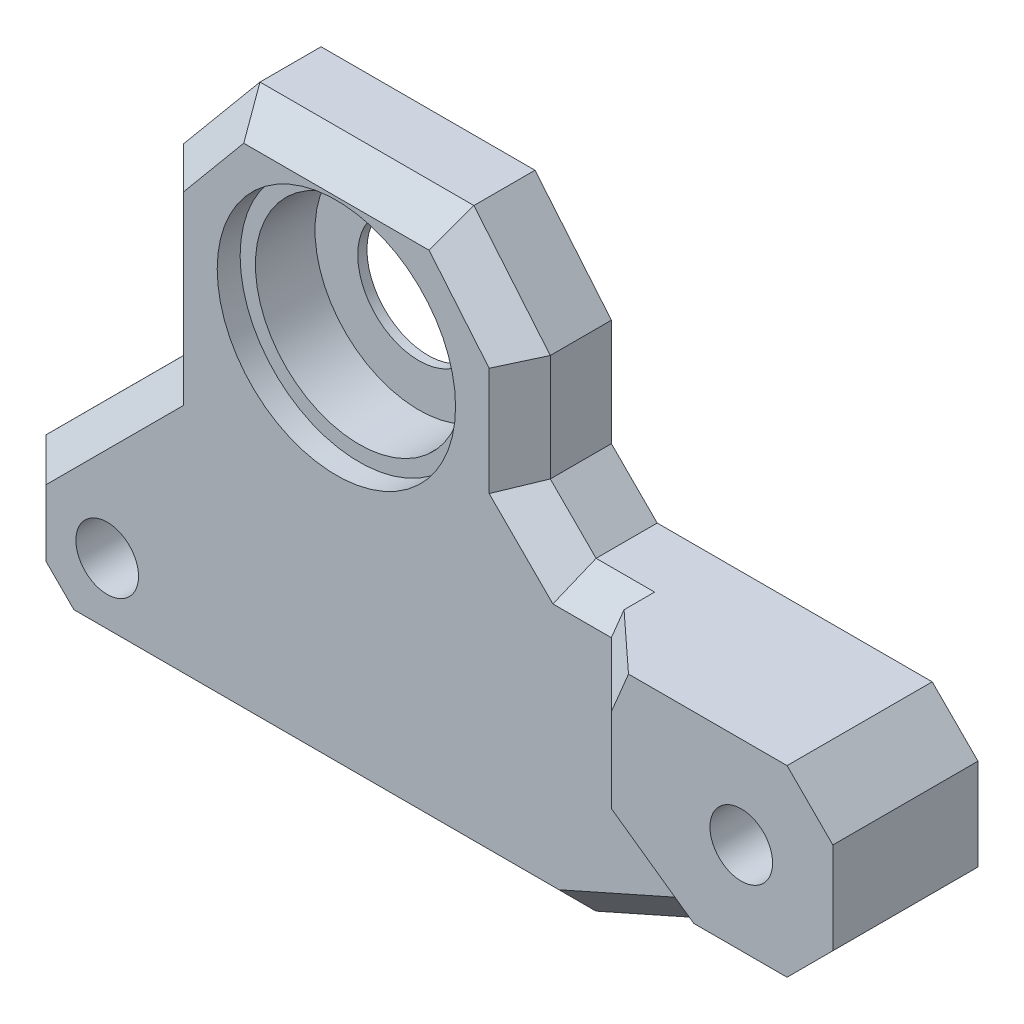
SolidWorks part; units mm, degrees
material "AISI 1020"
ref_plane "Front Plane" through (0, 0, 0) normal (0, 0, 1) x (1, 0, 0)
ref_plane "Top Plane" through (0, 0, 0) normal (0, 1, 0) x (1, 0, 0)
ref_plane "Right Plane" through (0, 0, 0) normal (1, 0, 0) x (0, 0, -1)
sketch "Sketch1" plane through (0, 0, 0) normal (0, 0, 1) x (1, 0, 0)
  line L0 (0, 14.0272) -> (0, -12.6873) construction
  line L1 (7, 15.5362) -> (-7, 15.5362)
  line L2 (-7, 15.5362) -> (-12, 9.5365)
  line L3 (-12, 0) -> (12, 0) construction
  line L4 (-12, 9.5365) -> (-12, -2.4635)
  line L6 (-21.0056, -11.4638) -> (-21.0056, -17.4638)
  line L7 (-21.0056, -17.4638) -> (-18.0093, -20.4638)
  line L8 (35.9944, -9.4616) -> (32.9963, -12.4598)
  line L9 (7, 15.5362) -> (12, 9.5365)
  line L10 (12, 9.5365) -> (12, 2.5365)
  line L11 (12, 2.5365) -> (14.9981, -0.4616)
  line L12 (14.9981, -0.4616) -> (32.9981, -0.4616)
  line L13 (32.9981, -0.4616) -> (35.9944, -3.4616)
  line L14 (35.9944, -3.4616) -> (35.9944, -9.4616)
  line L15 (32.9963, -12.4598) -> (14.9907, -20.4638)
  line L16 (14.9907, -20.4638) -> (-18.0093, -20.4638)
  line L17 (-12, -2.4635) -> (-21.0056, -11.4638)
  point P8 (0, 15.5362)
  point P13 (-12, -2.4635)
  dimension "D1" = 14
  dimension "D2" = 24
  dimension "D3" = 36
  dimension "D4" = 12
  dimension "D5" = 7.81
  dimension "D6" = 6
  dimension "D7" = 57
  dimension "D8" = 33
  dimension "D9" = 4.24
  dimension "D10" = 3
  dimension "D11" = 7
  dimension "D12" = 4.24
  dimension "D13" = 2.9981
  dimension "D14" = 18
  dimension "D15" = 4.24
  dimension "D16" = 3
  dimension "D17" = 6
  dimension "D18" = 4.24
  dimension "D19" = 2.9981
extrude "Boss-Extrude1" add sketch "Sketch1" against normal blind 4
sketch "Sketch2" plane through (0, 0, 0) normal (0, 0, 1) x (1, 0, 0)
  line L0 (7, 15.5362) -> (12, 9.5365) construction
  line L1 (12, 9.5365) -> (12, 2.5365) construction
  line L2 (12, 2.5365) -> (14.9981, -0.4616) construction
  line L3 (14.9981, -0.4616) -> (32.9981, -0.4616) construction
  line L4 (32.9981, -0.4616) -> (35.9944, -3.4616) construction
  line L5 (35.9944, -3.4616) -> (35.9944, -9.4616) construction
  line L6 (35.9944, -9.4616) -> (32.9963, -12.4598) construction
  line L7 (32.9963, -12.4598) -> (14.9907, -20.4638) construction
  line L8 (14.9907, -20.4638) -> (-18.0093, -20.4638) construction
  line L9 (-21.0056, -17.4638) -> (-18.0093, -20.4638) construction
  line L10 (-21.0056, -11.4638) -> (-21.0056, -17.4638) construction
  line L11 (-12, -2.4635) -> (-21.0056, -11.4638) construction
  line L12 (-12, 9.5365) -> (-12, -2.4635) construction
  line L13 (-7, 15.5362) -> (-12, 9.5365) construction
  line L14 (7, 15.5362) -> (-7, 15.5362) construction
  line L15 (7, 15.5362) -> (12, 9.5365)
  line L16 (12, 9.5365) -> (12, 2.5365)
  line L17 (12, 2.5365) -> (14.9981, -0.4616)
  line L18 (14.9981, -0.4616) -> (32.9981, -0.4616)
  line L19 (32.9981, -0.4616) -> (35.9944, -3.4616)
  line L20 (35.9944, -3.4616) -> (35.9944, -9.4616)
  line L21 (35.9944, -9.4616) -> (32.9963, -12.4598)
  line L22 (32.9963, -12.4598) -> (14.9907, -20.4638)
  line L23 (14.9907, -20.4638) -> (-18.0093, -20.4638)
  line L24 (-21.0056, -17.4638) -> (-18.0093, -20.4638)
  line L25 (-21.0056, -11.4638) -> (-21.0056, -17.4638)
  line L26 (-12, -2.4635) -> (-21.0056, -11.4638)
  line L27 (-12, 9.5365) -> (-12, -2.4635)
  line L28 (-7, 15.5362) -> (-12, 9.5365)
  line L29 (7, 15.5362) -> (-7, 15.5362)
extrude "Boss-Extrude2" add sketch "Sketch2" along normal blind 2 draft 45
sketch "Sketch4" plane through (0, 0, 0) normal (0, 0, 1) x (1, 0, 0)
  line L1 (14.9981, -0.4616) -> (32.9981, -0.4616) construction
  line L4 (32.9963, -12.4598) -> (20.8263, -12.4598)
  line L6 (18.8281, -0.4616) -> (32.9981, -0.4616)
  line L7 (32.9981, -0.4616) -> (35.9944, -3.4616)
  line L8 (35.9944, -3.4616) -> (35.9944, -9.4616)
  line L9 (35.9944, -9.4616) -> (32.9963, -12.4598)
  line L10 (18.8281, -0.4616) -> (17.9963, -2.4598)
  line L11 (17.9963, -2.4598) -> (17.9963, -10.4598)
  line L12 (17.9963, -10.4598) -> (20.8263, -12.4598)
  dimension "D1" = 14.17
  dimension "D2" = 12.17
  dimension "D3" = 8
  dimension "D4" = 2.83
  dimension "D5" = 2
extrude "Boss-Extrude3" add sketch "Sketch4" along normal blind 5.5
sketch "Sketch6" plane through (0, 0, -4) normal (0, 0, -1) x (-1, 0, 0)
  line L0 (0, 14.0272) -> (0, -12.6873) construction
  circle A0 centre (0, 5.54) radius 4
  point P1 (0, 15.5362)
  dimension "D2" = 5.54
  dimension "D1" = 15.5362
extrude "Cut-Extrude1" cut sketch "Sketch6" against normal blind 18.5
sketch "Sketch7" plane through (0, 0, 2) normal (0, 0, 1) x (1, 0, 0)
  circle A0 centre (0, 5.54) radius 6.8
extrude "Cut-Extrude2" cut sketch "Sketch7" against normal blind 5.4
sketch "Sketch8" plane through (0, 0, 2) normal (0, 0, 1) x (1, 0, 0)
  circle A0 centre (0, 5.54) radius 7.8
extrude "Cut-Extrude3" cut sketch "Sketch8" against normal blind 1.5
sketch "Sketch9" plane through (0, 0, 5.5) normal (0, 0, 1) x (1, 0, 0)
  line L0 (0, 14.0272) -> (0, -12.6873) construction
  circle A0 centre (-15, -14.46) radius 2.05
  circle A1 centre (30, -6.46) radius 2.05
  point P4 (0, 0)
  point P5 (0, 0)
  point P6 (0, 0)
  dimension "D1" = 45
  dimension "D2" = 12
  dimension "D3" = 20
  dimension "D4" = 15
extrude "Cut-Extrude4" cut sketch "Sketch9" against normal blind 15.5
sketch "Sketch10" plane through (0, 0, -4) normal (0, 0, -1) x (-1, 0, 0)
  circle A0 centre (15, -14.46) radius 4
extrude "Cut-Extrude5" cut sketch "Sketch10" against normal blind 2
sketch "Sketch11" plane through (0, 0, -4) normal (0, 0, -1) x (-1, 0, 0)
  circle A0 centre (-30, -6.46) radius 4
extrude "Cut-Extrude6" cut sketch "Sketch11" against normal blind 2
chamfer "Chamfer4" distance 3.5 angle 45 3 edges at (19.4113, -11.4598, 5.5) (18.4122, -1.4607, 5.5) (17.9963, -6.4598, 5.5)
equation "\"A\"= 100"
equation "\"B\"= 100"
equation "\"C\"= 100"
equation "\"D\"= 100"
equation "\"E\"= 100"
